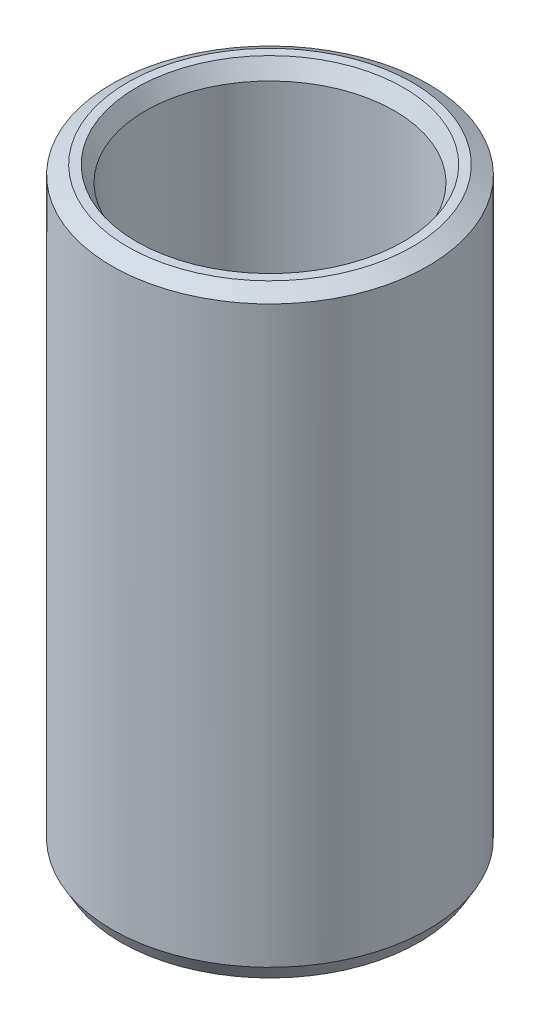
SolidWorks part; units mm, degrees
ref_plane "Front Plane" through (0, 0, 0) normal (0, 0, 1) x (1, 0, 0)
ref_plane "Top Plane" through (0, 0, 0) normal (0, 1, 0) x (1, 0, 0)
ref_plane "Right Plane" through (0, 0, 0) normal (1, 0, 0) x (0, 0, -1)
sketch "Sketch1" plane through (0, 0, 0) normal (0, 1, 0) x (1, 0, 0)
  circle A0 centre (0, 0) radius 60
  dimension "SLEEVE_OD" = 120
extrude "Boss-Extrude1" add sketch "Sketch1" along normal blind 227.5272
sketch "Sketch2" plane through (0, 0, 0) normal (0, 1, 0) x (1, 0, 0)
  circle A0 centre (0, 0) radius 47.2721
  dimension "BORE_D" = 94.5442
extrude "Cut-Extrude1" cut sketch "Sketch2" along normal through all
chamfer "Chamfer1" distance 3.4215 angle 60 4 edges at (0, 227.5272, 47.2721) (0, 0, 47.2721) (0, 0, 60) (0, 227.5272, 60) first distance on face at (0, 227.5272, 47.2721) first distance on face at (0, 0, 47.2721) first distance on face at (0, 227.5272, 60)
